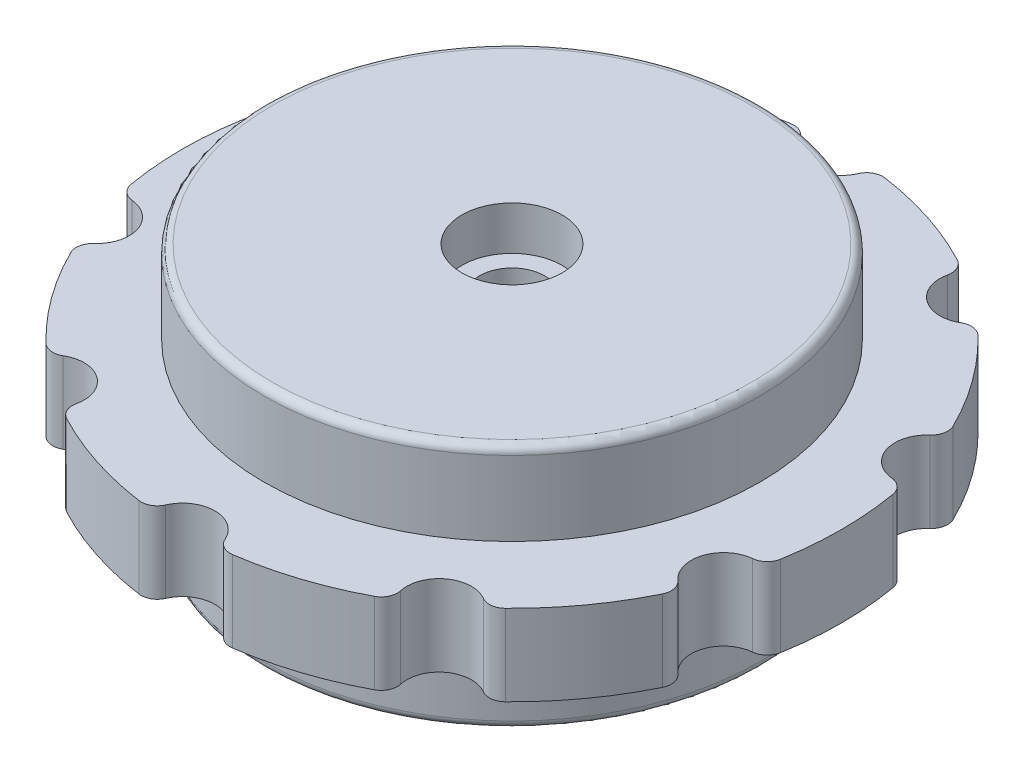
SolidWorks part; units mm, degrees
ref_plane "前视基准面" through (0, 0, 0) normal (0, 0, 1) x (1, 0, 0)
ref_plane "上视基准面" through (0, 0, 0) normal (0, 1, 0) x (1, 0, 0)
ref_plane "右视基准面" through (0, 0, 0) normal (1, 0, 0) x (0, 0, -1)
other "Configuration Table"
sketch "草图1" plane through (0, 0, 0) normal (0, 1, 0) x (1, 0, 0)
  circle A0 centre (0, 0) radius 15.3
  circle A1 centre (0, 0) radius 20.35
  circle A2 centre (0, 0) radius 13.7
  circle A3 centre (0, 20.35) radius 2
  dimension "D1" = 30.6
  dimension "D2" = 40.7
  dimension "D3" = 1.6
  dimension "D4" = 4
extrude "凸台-拉伸1" add sketch "草图1" along normal mid plane 15.2 contours A0 | A2
extrude "凸台-拉伸2" add sketch "草图1<3>" along normal mid plane 5 contours A1
sketch "草图1<3>" plane through (0, 0, 0) normal (0, 1, 0) x (1, 0, 0) same geometry as "草图1"
extrude "切除-拉伸1" cut sketch "草图1<4>" against normal through all both and the other way through all contours A3
sketch "草图1<4>" plane through (0, 0, 0) normal (0, 1, 0) x (1, 0, 0) same geometry as "草图1"
fillet "圆角1" radius 1 2 edges at (1.9976, 0, -20.2517) (-1.9976, 0, -20.2517)
pattern_circular "阵列(圆周)1" count 10 over 360 about axis through (0, 2.5, 0) along (0, -1, 0) of "切除-拉伸1", "圆角1"
fillet "圆角2" radius 0.5 2 edges at (0, -7.6, 15.3) (0, 7.6, 15.3)
extrude "凸台-拉伸3" add sketch "草图1<5>" along normal mid plane 7.8 contours A2
sketch "草图1<5>" plane through (0, 0, 0) normal (0, 1, 0) x (1, 0, 0) same geometry as "草图1"
extrude "凸台-拉伸5" add sketch "草图1<6>" along normal up to surface (7.6 mm away) from surface contours A2 up to face at (0, 7.6, 14.8) starting at face at (0, -7.6, 14.8)
sketch "草图1<6>" plane through (0, 0, 0) normal (0, 1, 0) x (1, 0, 0) same geometry as "草图1"
sketch "草图2" plane through (0, 2.5, 0) normal (0, 1, 0) x (1, 0, 0)
  line L0 (0, 20.35) -> (11.9614, 16.4635)
  line L1 (-11.9614, 16.4635) -> (0, 20.35)
  arc A0 (-1.834, 19.5523) -> (1.834, 19.5523) centre (0, 20.35) ccw construction
  arc A1 (10.0088, 16.8962) -> (12.9763, 14.7401) centre (11.9614, 16.4635) ccw construction
  arc A2 (-12.9763, 14.7401) -> (-10.0088, 16.8962) centre (-11.9614, 16.4635) ccw construction
  dimension "D1" = 12.577
  dimension "D2" = 12.577
sketch "草图4" plane through (0, -7.6, 0) normal (0, -1, 0) x (1, 0, 0)
  circle A0 centre (0, 0) radius 2
  circle A1 centre (0, 0) radius 3.1
  dimension "D1" = 4
  dimension "D2" = 6.2
extrude "切除-拉伸3" cut sketch "草图4" against normal through all contours A0
extrude "切除-拉伸4" cut sketch "草图4<3>" against normal blind 2.7 contours A1
sketch "草图4<3>" plane through (0, -7.6, 0) normal (0, -1, 0) x (1, 0, 0) same geometry as "草图4"
extrude "切除-拉伸5" cut sketch "草图4<4>" along normal blind 2.7 from surface contours A1 starting at face at (0, 7.6, -2)
sketch "草图4<4>" plane through (0, -7.6, 0) normal (0, -1, 0) x (1, 0, 0) same geometry as "草图4"
